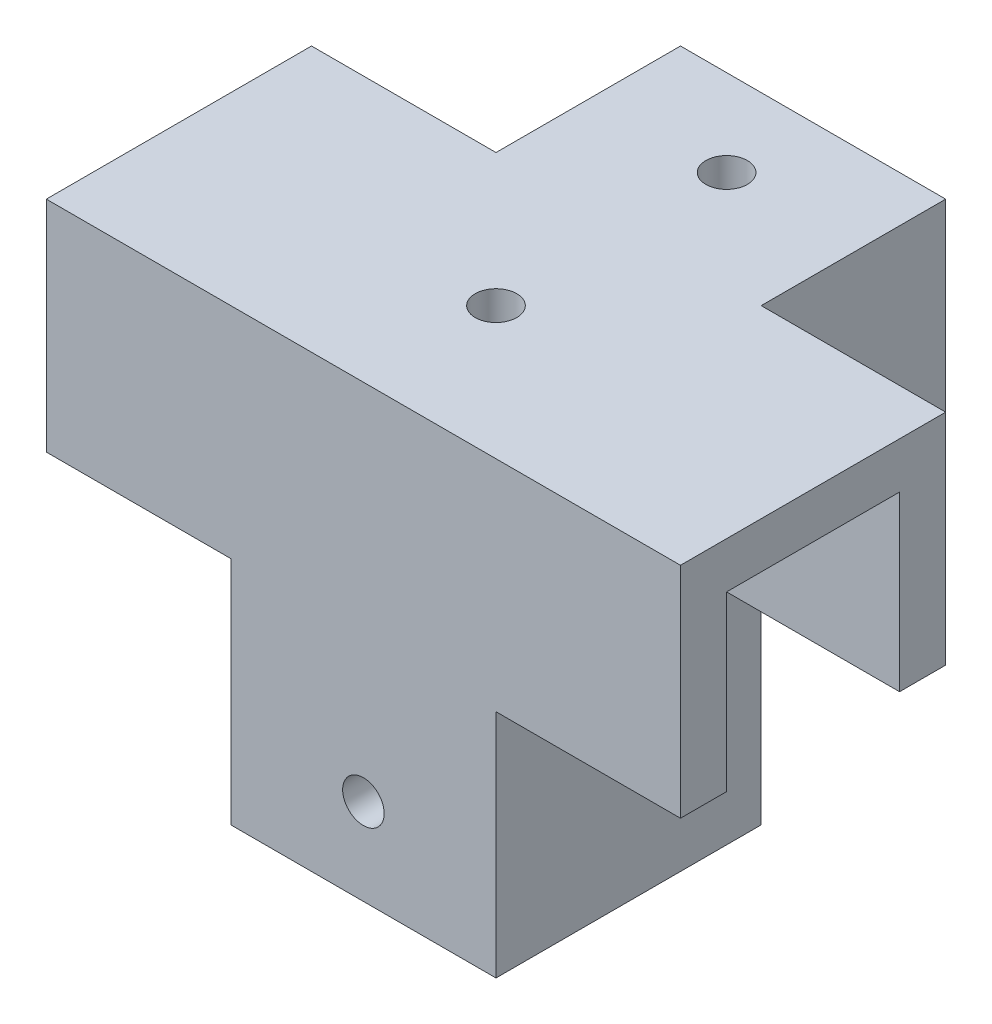
SolidWorks part; units mm, degrees
ref_plane "前视基准面" through (0, 0, 0) normal (0, 0, 1) x (1, 0, 0)
ref_plane "上视基准面" through (0, 0, 0) normal (0, 1, 0) x (1, 0, 0)
ref_plane "右视基准面" through (0, 0, 0) normal (1, 0, 0) x (0, 0, -1)
sketch "草图1" plane through (0, 0, 0) normal (0, 1, 0) x (1, 0, 0)
  line L1 (-22.0308, -9.6154) -> (32.9692, -9.6154)
  line L2 (-22.0308, -9.6154) -> (-22.0308, -13.6154)
  line L3 (-22.0308, -13.6154) -> (32.9692, -13.6154)
  line L4 (32.9692, -9.6154) -> (32.9692, -13.6154)
  line L5 (-22.0308, 9.3846) -> (-6.0308, 9.3846)
  line L6 (-22.0308, 9.3846) -> (-22.0308, 5.3846)
  line L7 (-22.0308, 5.3846) -> (-2.0308, 5.3846)
  line L8 (-2.0308, 9.3846) -> (-2.0308, 5.3846)
  line L9 (-2.0308, 5.3846) -> (-6.0308, 5.3846)
  line L10 (-2.0308, 5.3846) -> (-2.0308, 25.3846)
  line L11 (-2.0308, 25.3846) -> (-6.0308, 25.3846)
  line L12 (-6.0308, 9.3846) -> (-6.0308, 25.3846)
  line L13 (32.9692, 5.3846) -> (12.9692, 5.3846)
  line L14 (32.9692, 5.3846) -> (32.9692, 9.3846)
  line L15 (32.9692, 9.3846) -> (16.9692, 9.3846)
  line L16 (12.9692, 5.3846) -> (12.9692, 8.7692)
  line L17 (12.9692, 5.3846) -> (22.6154, 5.3846)
  line L18 (12.9692, 5.3846) -> (12.9692, 25.3846)
  line L19 (12.9692, 25.3846) -> (16.9692, 25.3846)
  line L20 (16.9692, 9.3846) -> (16.9692, 25.3846)
  dimension "D1" = 4
  dimension "D2" = 4
  dimension "D3" = 4
  dimension "D4" = 4
  dimension "D5" = 4
  dimension "D6" = 15
  dimension "D7" = 15
  dimension "D8" = 20
  dimension "D9" = 16
  dimension "D10" = 16
  dimension "D11" = 20
  dimension "D12" = 0
  dimension "D13" = 0
extrude "凸台-拉伸1" add sketch "草图1" along normal blind 15 contours L12 L5 L6 L7 L8 L10 L11 | L15 L20 L19 L18 L16 L13 L14 | L4 L1 L2 L3 region at (5.4692, 0, 11.6154) region at (-14.0308, 0, -9.1018) region at (27.7923, 0, -5.6675)
sketch "草图2" plane through (0, 15, 0) normal (0, 1, 0) x (1, 0, 0)
  line L1 (-22.0308, 9.3846) -> (32.9692, 9.3846)
  line L2 (-22.0308, 9.3846) -> (-22.0308, -13.6154)
  line L3 (-22.0308, -13.6154) -> (32.9692, -13.6154)
  line L4 (32.9692, 9.3846) -> (32.9692, -13.6154)
  line L5 (-6.0308, 25.3846) -> (16.9692, 25.3846)
  line L6 (-6.0308, 25.3846) -> (-6.0308, 9.3846)
  line L7 (-6.0308, 9.3846) -> (16.9692, 9.3846)
  line L8 (16.9692, 25.3846) -> (16.9692, 9.3846)
  line M1 (-6.0308, 25.3846) -> (-6.0308, 9.3846)
  line M2 (-6.0308, 9.3846) -> (-22.0308, 9.3846)
  line M3 (-22.0308, 9.3846) -> (-22.0308, 5.3846)
  line M4 (-22.0308, 5.3846) -> (-2.0308, 5.3846)
  line M5 (-2.0308, 5.3846) -> (-2.0308, 25.3846)
  line M6 (-2.0308, 25.3846) -> (-6.0308, 25.3846)
extrude "凸台-拉伸2" add sketch "草图2" along normal blind 4 contours L1 M1 M5 M6 | L8 L5 L1 M5 | L4 L1 L2 L3 M5 M4 | L1 M2 M3 M4 M5 region at (-12.0308, 15, -7.3846) region at (-4.0308, 15, -17.3846) region at (6.6507, 15, 2.7567) region at (7.4692, 15, -17.3846)
sketch "草图3" plane through (0, 0, 0) normal (0, -1, 0) x (1, 0, 0)
  line L0 (-22.0308, 13.6154) -> (32.9692, 13.6154) construction
  line L1 (16.9692, -9.3846) -> (-6.0308, -9.3846)
  line L2 (16.9692, -9.3846) -> (16.9692, 13.6154)
  line L3 (16.9692, 13.6154) -> (-6.0308, 13.6154)
  line L4 (-6.0308, -9.3846) -> (-6.0308, 13.6154)
  line L5 (-22.0308, 9.6154) -> (32.9692, 9.6154) construction
  line L6 (12.9692, -5.3846) -> (-2.0308, -5.3846)
  line L7 (12.9692, -5.3846) -> (12.9692, 9.6154)
  line L8 (12.9692, 9.6154) -> (-2.0308, 9.6154)
  line L9 (-2.0308, -5.3846) -> (-2.0308, 9.6154)
  dimension "D1" = 23
  dimension "D2" = 15
extrude "凸台-拉伸3" add sketch "草图3" along normal blind 20
sketch "草图4" plane through (0, 19, 0) normal (0, 1, 0) x (1, 0, 0)
  line L0 (16.9692, 25.3846) -> (-6.0308, 25.3846) construction
  circle A0 centre (5.4692, 17.8846) radius 1.8
  circle A1 centre (5.4692, -2.1154) radius 1.8
  dimension "D1" = 3.6
  dimension "D2" = 3.6
  dimension "D3" = 7.5
extrude "切除-拉伸1" cut sketch "草图4" against normal blind 20
sketch "草图5" plane through (0, 0, 13.6154) normal (0, 0, 1) x (1, 0, 0)
  line L0 (16.9692, -20) -> (-6.0308, -20) construction
  circle A0 centre (5.4692, -12.5) radius 1.8
  dimension "D1" = 3.6
  dimension "D2" = 7.5
extrude "切除-拉伸2" cut sketch "草图5" against normal blind 27
